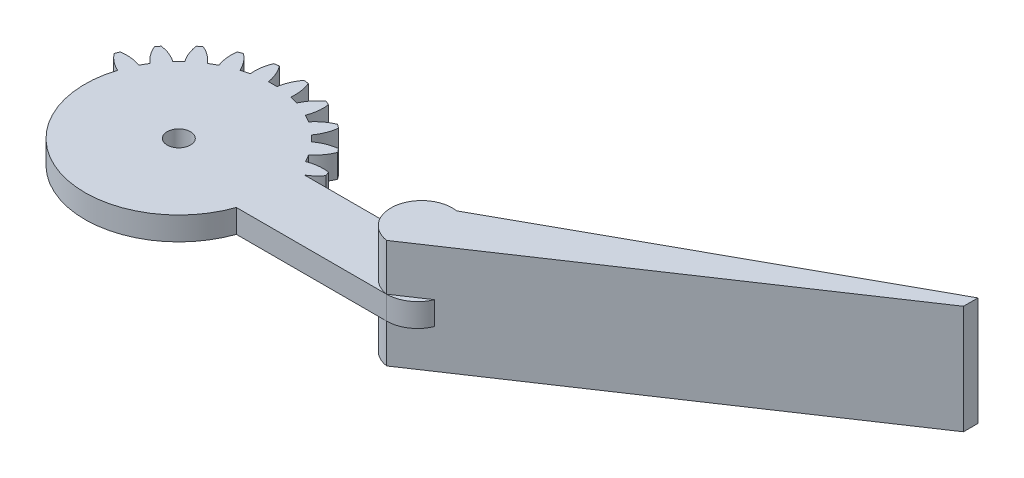
SolidWorks part; units mm, degrees
ref_plane "Front Plane" through (0, 0, 0) normal (0, 0, 1) x (1, 0, 0)
ref_plane "Top Plane" through (0, 0, 0) normal (0, 1, 0) x (1, 0, 0)
ref_plane "Right Plane" through (0, 0, 0) normal (1, 0, 0) x (0, 0, -1)
sketch "Sketch1" plane through (0, 0, 0) normal (0, 1, 0) x (1, 0, 0)
  line L0 (20.6437, 4) -> (2.0816, 4)
  line L1 (2.0816, -4) -> (20.6437, -4)
  arc A0 (2.0816, 4) -> (3.5217, 5.3071) centre (-0.7683, 8.5867) ccw
  arc A1 (3.5217, 5.3071) -> (3.2829, 5.8838) centre (-10.1063, 0) ccw
  arc A2 (3.2829, 5.8838) -> (0.6271, 5.5703) centre (2.5684, 0.5313) ccw
  arc A3 (0.6271, 5.5703) -> (0.0844, 6.5103) centre (-10.1063, 0) ccw
  arc A4 (0.0844, 6.5103) -> (1.6838, 8.6535) centre (-3.3089, 10.711) ccw
  arc A5 (1.6838, 8.6535) -> (1.3038, 9.1487) centre (-10.1063, 0) ccw
  arc A6 (1.3038, 9.1487) -> (-1.1803, 8.1585) centre (1.999, 3.7936) ccw
  arc A7 (-1.1803, 8.1585) -> (-1.9479, 8.926) centre (-10.1063, 0) ccw
  arc A8 (-1.9479, 8.926) -> (-0.9576, 11.4102) centre (-6.3127, 12.1053) ccw
  arc A9 (-0.9576, 11.4102) -> (-1.4528, 11.7901) centre (-10.1063, 0) ccw
  arc A10 (-1.4528, 11.7901) -> (-3.596, 10.1907) centre (0.6046, 6.7975) ccw
  arc A11 (-3.596, 10.1907) -> (-4.5361, 10.7334) centre (-10.1063, 0) ccw
  arc A12 (-4.5361, 10.7334) -> (-4.2225, 13.3892) centre (-9.5751, 12.6747) ccw
  arc A13 (-4.2225, 13.3892) -> (-4.7992, 13.6281) centre (-10.1063, 0) ccw
  arc A14 (-4.7992, 13.6281) -> (-6.4554, 11.5285) centre (-1.5196, 9.3381) ccw
  arc A15 (-6.4554, 11.5285) -> (-7.5039, 11.8094) centre (-10.1063, 0) ccw
  arc A16 (-7.5039, 11.8094) -> (-7.8884, 14.4558) centre (-12.8736, 12.3803) ccw
  arc A17 (-7.8884, 14.4558) -> (-8.5072, 14.5373) centre (-10.1063, 0) ccw
  arc A18 (-8.5072, 14.5373) -> (-9.5636, 12.0806) centre (-4.2291, 11.2423) ccw
  arc A19 (-9.5636, 12.0806) -> (-10.6491, 12.0806) centre (-10.1063, 0) ccw
  arc A20 (-10.6491, 12.0806) -> (-11.7054, 14.5373) centre (-15.9836, 11.2423) ccw
  arc A21 (-11.7054, 14.5373) -> (-12.3243, 14.4558) centre (-10.1063, 0) ccw
  arc A22 (-12.3243, 14.4558) -> (-12.7088, 11.8094) centre (-7.3391, 12.3803) ccw
  arc A23 (-12.7088, 11.8094) -> (-13.7573, 11.5285) centre (-10.1063, 0) ccw
  arc A24 (-13.7573, 11.5285) -> (-15.4135, 13.6281) centre (-18.6931, 9.3381) ccw
  arc A25 (-15.4135, 13.6281) -> (-15.9901, 13.3892) centre (-10.1063, 0) ccw
  arc A26 (-15.9901, 13.3892) -> (-15.6766, 10.7334) centre (-10.6376, 12.6747) ccw
  arc A27 (-15.6766, 10.7334) -> (-16.6166, 10.1907) centre (-10.1063, 0) ccw
  arc A28 (-16.6166, 10.1907) -> (-18.7599, 11.7901) centre (-20.8173, 6.7975) ccw
  arc A29 (-18.7599, 11.7901) -> (-19.255, 11.4102) centre (-10.1063, 0) ccw
  arc A30 (-19.255, 11.4102) -> (-18.2648, 8.926) centre (-13.9, 12.1053) ccw
  arc A31 (-18.2648, 8.926) -> (-19.0324, 8.1585) centre (-10.1063, 0) ccw
  arc A32 (-19.0324, 8.1585) -> (-21.5165, 9.1487) centre (-22.2117, 3.7936) ccw
  arc A33 (-21.5165, 9.1487) -> (-21.8965, 8.6535) centre (-10.1063, 0) ccw
  arc A34 (-21.8965, 8.6535) -> (-20.2971, 6.5103) centre (-16.9038, 10.711) ccw
  arc A35 (-20.2971, 6.5103) -> (-20.8398, 5.5703) centre (-10.1063, 0) ccw
  arc A36 (-20.8398, 5.5703) -> (-23.4956, 5.8838) centre (-22.7811, 0.5313) ccw
  arc A37 (-23.4956, 5.8838) -> (-23.7344, 5.3071) centre (-10.1063, 0) ccw
  arc A38 (-23.7344, 5.3071) -> (-21.6348, 3.6509) centre (-19.4444, 8.5867) ccw
  arc A39 (-21.6348, 3.6509) -> (-21.9157, 2.6025) centre (-10.1063, 0) ccw
  arc A40 (-21.9157, 2.6025) -> (-24.5622, 2.2179) centre (-22.4867, -2.7673) ccw
  arc A41 (-24.5622, 2.2179) -> (-24.6437, 1.5991) centre (-10.1063, 0) ccw
  arc A42 (-24.6437, 1.5991) -> (-22.1869, 0.5427) centre (-21.3486, 5.8773) ccw
  arc A43 (-22.1869, 0.5427) -> (-22.1869, -0.5427) centre (-10.1063, 0) ccw
  arc A44 (-22.1869, -0.5427) -> (-24.6437, -1.5991) centre (-21.3486, -5.8773) ccw
  arc A45 (-24.6437, -1.5991) -> (-24.5622, -2.2179) centre (-10.1063, 0) ccw
  arc A46 (-24.5622, -2.2179) -> (-21.9157, -2.6025) centre (-22.4867, 2.7673) ccw
  arc A47 (-21.9157, -2.6025) -> (-21.6348, -3.6509) centre (-10.1063, 0) ccw
  arc A48 (-21.6348, -3.6509) -> (-23.7344, -5.3071) centre (-19.4444, -8.5867) ccw
  arc A49 (-23.7344, -5.3071) -> (-23.4956, -5.8838) centre (-10.1063, 0) ccw
  arc A50 (-23.4956, -5.8838) -> (-20.8398, -5.5703) centre (-22.7811, -0.5313) ccw
  arc A51 (-20.8398, -5.5703) -> (-20.2971, -6.5103) centre (-10.1063, 0) ccw
  arc A52 (-20.2971, -6.5103) -> (-21.8965, -8.6535) centre (-16.9038, -10.711) ccw
  arc A53 (-21.8965, -8.6535) -> (-21.5165, -9.1487) centre (-10.1063, 0) ccw
  arc A54 (-21.5165, -9.1487) -> (-19.0324, -8.1585) centre (-22.2117, -3.7936) ccw
  arc A55 (-19.0324, -8.1585) -> (-18.2648, -8.926) centre (-10.1063, 0) ccw
  arc A56 (-18.2648, -8.926) -> (-19.255, -11.4102) centre (-13.9, -12.1053) ccw
  arc A57 (-19.255, -11.4102) -> (-18.7599, -11.7901) centre (-10.1063, 0) ccw
  arc A58 (-18.7599, -11.7901) -> (-16.6166, -10.1907) centre (-20.8173, -6.7975) ccw
  arc A59 (-16.6166, -10.1907) -> (-15.6766, -10.7334) centre (-10.1063, 0) ccw
  arc A60 (-15.6766, -10.7334) -> (-15.9901, -13.3892) centre (-10.6376, -12.6747) ccw
  arc A61 (-15.9901, -13.3892) -> (-15.4135, -13.6281) centre (-10.1063, 0) ccw
  arc A62 (-15.4135, -13.6281) -> (-13.7573, -11.5285) centre (-18.6931, -9.3381) ccw
  arc A63 (-13.7573, -11.5285) -> (-12.7088, -11.8094) centre (-10.1063, 0) ccw
  arc A64 (-12.7088, -11.8094) -> (-12.3243, -14.4558) centre (-7.3391, -12.3803) ccw
  arc A65 (-12.3243, -14.4558) -> (-11.7054, -14.5373) centre (-10.1063, 0) ccw
  arc A66 (-11.7054, -14.5373) -> (-10.6491, -12.0806) centre (-15.9836, -11.2423) ccw
  arc A67 (-10.6491, -12.0806) -> (-9.5636, -12.0806) centre (-10.1063, 0) ccw
  arc A68 (-9.5636, -12.0806) -> (-8.5072, -14.5373) centre (-4.2291, -11.2423) ccw
  arc A69 (-8.5072, -14.5373) -> (-7.8884, -14.4558) centre (-10.1063, 0) ccw
  arc A70 (-7.8884, -14.4558) -> (-7.5039, -11.8094) centre (-12.8736, -12.3803) ccw
  arc A71 (-7.5039, -11.8094) -> (-6.4554, -11.5285) centre (-10.1063, 0) ccw
  arc A72 (-6.4554, -11.5285) -> (-4.7992, -13.6281) centre (-1.5196, -9.3381) ccw
  arc A73 (-4.7992, -13.6281) -> (-4.2225, -13.3892) centre (-10.1063, 0) ccw
  arc A74 (-4.2225, -13.3892) -> (-4.5361, -10.7334) centre (-9.5751, -12.6747) ccw
  arc A75 (-4.5361, -10.7334) -> (-3.596, -10.1907) centre (-10.1063, 0) ccw
  arc A76 (-3.596, -10.1907) -> (-1.4528, -11.7901) centre (0.6046, -6.7975) ccw
  arc A77 (-1.4528, -11.7901) -> (-0.9576, -11.4102) centre (-10.1063, 0) ccw
  arc A78 (-0.9576, -11.4102) -> (-1.9479, -8.926) centre (-6.3127, -12.1053) ccw
  arc A79 (-1.9479, -8.926) -> (-1.1803, -8.1585) centre (-10.1063, 0) ccw
  arc A80 (-1.1803, -8.1585) -> (1.3038, -9.1487) centre (1.999, -3.7936) ccw
  arc A81 (1.3038, -9.1487) -> (1.6838, -8.6535) centre (-10.1063, 0) ccw
  arc A82 (1.6838, -8.6535) -> (0.0844, -6.5103) centre (-3.3089, -10.711) ccw
  arc A83 (0.0844, -6.5103) -> (0.6271, -5.5703) centre (-10.1063, 0) ccw
  arc A84 (0.6271, -5.5703) -> (3.2829, -5.8838) centre (2.5684, -0.5313) ccw
  arc A85 (3.2829, -5.8838) -> (3.5217, -5.3071) centre (-10.1063, 0) ccw
  arc A86 (3.5217, -5.3071) -> (2.0816, -4) centre (-0.7683, -8.5867) ccw
  arc A87 (20.6437, -4) -> (20.6437, 4) centre (20.6437, 0) ccw
  circle A88 centre (-10.1063, 0) radius 1.5
  circle A89 centre (20.6437, 0) radius 1.5
  dimension "D1" = 3
  dimension "D2" = 3
extrude "Boss-Extrude1" add sketch "Sketch1" along normal blind 3
sketch "Sketch2" plane through (0, 3, 0) normal (0, 1, 0) x (1, 0, 0)
  line L0 (2.0816, -4) -> (1.3057, -4)
  line L2 (20.6437, 4) -> (2.0816, 4)
  line L3 (2.0816, -4) -> (20.6437, -4)
  line L4 (20.6437, 4) -> (2.0816, 4)
  line L5 (2.0816, -4) -> (20.6437, -4)
  circle A0 centre (-10.1063, 0) radius 12.0927
  arc A88 (20.6437, -4) -> (20.6437, 4) centre (20.6437, 0) ccw
  arc A89 (2.0816, 4) -> (3.5217, 5.3071) centre (-0.7683, 8.5867) ccw
  arc A90 (3.5217, 5.3071) -> (3.2829, 5.8838) centre (-10.1063, 0) ccw
  arc A91 (3.2829, 5.8838) -> (0.6271, 5.5703) centre (2.5684, 0.5313) ccw
  arc A92 (0.6271, 5.5703) -> (0.0844, 6.5103) centre (-10.1063, 0) ccw
  arc A93 (0.0844, 6.5103) -> (1.6838, 8.6535) centre (-3.3089, 10.711) ccw
  arc A94 (1.6838, 8.6535) -> (1.3038, 9.1487) centre (-10.1063, 0) ccw
  arc A95 (1.3038, 9.1487) -> (-1.1803, 8.1585) centre (1.999, 3.7936) ccw
  arc A96 (-1.1803, 8.1585) -> (-1.9479, 8.926) centre (-10.1063, 0) ccw
  arc A97 (-1.9479, 8.926) -> (-0.9576, 11.4102) centre (-6.3127, 12.1053) ccw
  arc A98 (-0.9576, 11.4102) -> (-1.4528, 11.7901) centre (-10.1063, 0) ccw
  arc A99 (-1.4528, 11.7901) -> (-3.596, 10.1907) centre (0.6046, 6.7975) ccw
  arc A100 (-3.596, 10.1907) -> (-4.5361, 10.7334) centre (-10.1063, 0) ccw
  arc A101 (-4.5361, 10.7334) -> (-4.2225, 13.3892) centre (-9.5751, 12.6747) ccw
  arc A102 (-4.2225, 13.3892) -> (-4.7992, 13.6281) centre (-10.1063, 0) ccw
  arc A103 (-4.7992, 13.6281) -> (-6.4554, 11.5285) centre (-1.5196, 9.3381) ccw
  arc A104 (-6.4554, 11.5285) -> (-7.5039, 11.8094) centre (-10.1063, 0) ccw
  arc A105 (-7.5039, 11.8094) -> (-7.8884, 14.4558) centre (-12.8736, 12.3803) ccw
  arc A106 (-7.8884, 14.4558) -> (-8.5072, 14.5373) centre (-10.1063, 0) ccw
  arc A107 (-8.5072, 14.5373) -> (-9.5636, 12.0806) centre (-4.2291, 11.2423) ccw
  arc A108 (-9.5636, 12.0806) -> (-10.6491, 12.0806) centre (-10.1063, 0) ccw
  arc A109 (-10.6491, 12.0806) -> (-11.7054, 14.5373) centre (-15.9836, 11.2423) ccw
  arc A110 (-11.7054, 14.5373) -> (-12.3243, 14.4558) centre (-10.1063, 0) ccw
  arc A111 (-12.3243, 14.4558) -> (-12.7088, 11.8094) centre (-7.3391, 12.3803) ccw
  arc A112 (-12.7088, 11.8094) -> (-13.7573, 11.5285) centre (-10.1063, 0) ccw
  arc A113 (-13.7573, 11.5285) -> (-15.4135, 13.6281) centre (-18.6931, 9.3381) ccw
  arc A114 (-15.4135, 13.6281) -> (-15.9901, 13.3892) centre (-10.1063, 0) ccw
  arc A115 (-15.9901, 13.3892) -> (-15.6766, 10.7334) centre (-10.6376, 12.6747) ccw
  arc A116 (-15.6766, 10.7334) -> (-16.6166, 10.1907) centre (-10.1063, 0) ccw
  arc A117 (-16.6166, 10.1907) -> (-18.7599, 11.7901) centre (-20.8173, 6.7975) ccw
  arc A118 (-18.7599, 11.7901) -> (-19.255, 11.4102) centre (-10.1063, 0) ccw
  arc A119 (-19.255, 11.4102) -> (-18.2648, 8.926) centre (-13.9, 12.1053) ccw
  arc A120 (-18.2648, 8.926) -> (-19.0324, 8.1585) centre (-10.1063, 0) ccw
  arc A121 (-19.0324, 8.1585) -> (-21.5165, 9.1487) centre (-22.2117, 3.7936) ccw
  arc A122 (-21.5165, 9.1487) -> (-21.8965, 8.6535) centre (-10.1063, 0) ccw
  arc A123 (-21.8965, 8.6535) -> (-20.2971, 6.5103) centre (-16.9038, 10.711) ccw
  arc A124 (-20.2971, 6.5103) -> (-20.8398, 5.5703) centre (-10.1063, 0) ccw
  arc A125 (-20.8398, 5.5703) -> (-23.4956, 5.8838) centre (-22.7811, 0.5313) ccw
  arc A126 (-23.4956, 5.8838) -> (-23.7344, 5.3071) centre (-10.1063, 0) ccw
  arc A127 (-23.7344, 5.3071) -> (-21.6348, 3.6509) centre (-19.4444, 8.5867) ccw
  arc A128 (-21.6348, 3.6509) -> (-21.9157, 2.6025) centre (-10.1063, 0) ccw
  arc A129 (-21.9157, 2.6025) -> (-24.5622, 2.2179) centre (-22.4867, -2.7673) ccw
  arc A130 (-24.5622, 2.2179) -> (-24.6437, 1.5991) centre (-10.1063, 0) ccw
  arc A131 (-24.6437, 1.5991) -> (-22.1869, 0.5427) centre (-21.3486, 5.8773) ccw
  arc A132 (-22.1869, 0.5427) -> (-22.1869, -0.5427) centre (-10.1063, 0) ccw
  arc A133 (-22.1869, -0.5427) -> (-24.6437, -1.5991) centre (-21.3486, -5.8773) ccw
  arc A134 (-24.6437, -1.5991) -> (-24.5622, -2.2179) centre (-10.1063, 0) ccw
  arc A135 (-24.5622, -2.2179) -> (-21.9157, -2.6025) centre (-22.4867, 2.7673) ccw
  arc A136 (-21.9157, -2.6025) -> (-21.6348, -3.6509) centre (-10.1063, 0) ccw
  arc A137 (-21.6348, -3.6509) -> (-23.7344, -5.3071) centre (-19.4444, -8.5867) ccw
  arc A138 (-23.7344, -5.3071) -> (-23.4956, -5.8838) centre (-10.1063, 0) ccw
  arc A139 (-23.4956, -5.8838) -> (-20.8398, -5.5703) centre (-22.7811, -0.5313) ccw
  arc A140 (-20.8398, -5.5703) -> (-20.2971, -6.5103) centre (-10.1063, 0) ccw
  arc A141 (-20.2971, -6.5103) -> (-21.8965, -8.6535) centre (-16.9038, -10.711) ccw
  arc A142 (-21.8965, -8.6535) -> (-21.5165, -9.1487) centre (-10.1063, 0) ccw
  arc A143 (-21.5165, -9.1487) -> (-19.0324, -8.1585) centre (-22.2117, -3.7936) ccw
  arc A144 (-19.0324, -8.1585) -> (-18.2648, -8.926) centre (-10.1063, 0) ccw
  arc A145 (-18.2648, -8.926) -> (-19.255, -11.4102) centre (-13.9, -12.1053) ccw
  arc A146 (-19.255, -11.4102) -> (-18.7599, -11.7901) centre (-10.1063, 0) ccw
  arc A147 (-18.7599, -11.7901) -> (-16.6166, -10.1907) centre (-20.8173, -6.7975) ccw
  arc A148 (-16.6166, -10.1907) -> (-15.6766, -10.7334) centre (-10.1063, 0) ccw
  arc A149 (-15.6766, -10.7334) -> (-15.9901, -13.3892) centre (-10.6376, -12.6747) ccw
  arc A150 (-15.9901, -13.3892) -> (-15.4135, -13.6281) centre (-10.1063, 0) ccw
  arc A151 (-15.4135, -13.6281) -> (-13.7573, -11.5285) centre (-18.6931, -9.3381) ccw
  arc A152 (-13.7573, -11.5285) -> (-12.7088, -11.8094) centre (-10.1063, 0) ccw
  arc A153 (-12.7088, -11.8094) -> (-12.3243, -14.4558) centre (-7.3391, -12.3803) ccw
  arc A154 (-12.3243, -14.4558) -> (-11.7054, -14.5373) centre (-10.1063, 0) ccw
  arc A155 (-11.7054, -14.5373) -> (-10.6491, -12.0806) centre (-15.9836, -11.2423) ccw
  arc A156 (-10.6491, -12.0806) -> (-9.5636, -12.0806) centre (-10.1063, 0) ccw
  arc A157 (-9.5636, -12.0806) -> (-8.5072, -14.5373) centre (-4.2291, -11.2423) ccw
  arc A158 (-8.5072, -14.5373) -> (-7.8884, -14.4558) centre (-10.1063, 0) ccw
  arc A159 (-7.8884, -14.4558) -> (-7.5039, -11.8094) centre (-12.8736, -12.3803) ccw
  arc A160 (-7.5039, -11.8094) -> (-6.4554, -11.5285) centre (-10.1063, 0) ccw
  arc A161 (-6.4554, -11.5285) -> (-4.7992, -13.6281) centre (-1.5196, -9.3381) ccw
  arc A162 (-4.7992, -13.6281) -> (-4.2225, -13.3892) centre (-10.1063, 0) ccw
  arc A163 (-4.2225, -13.3892) -> (-4.5361, -10.7334) centre (-9.5751, -12.6747) ccw
  arc A164 (-4.5361, -10.7334) -> (-3.596, -10.1907) centre (-10.1063, 0) ccw
  arc A165 (-3.596, -10.1907) -> (-1.4528, -11.7901) centre (0.6046, -6.7975) ccw
  arc A166 (-1.4528, -11.7901) -> (-0.9576, -11.4102) centre (-10.1063, 0) ccw
  arc A167 (-0.9576, -11.4102) -> (-1.9479, -8.926) centre (-6.3127, -12.1053) ccw
  arc A168 (-1.9479, -8.926) -> (-1.1803, -8.1585) centre (-10.1063, 0) ccw
  arc A169 (-1.1803, -8.1585) -> (1.3038, -9.1487) centre (1.999, -3.7936) ccw
  arc A170 (1.3038, -9.1487) -> (1.6838, -8.6535) centre (-10.1063, 0) ccw
  arc A171 (1.6838, -8.6535) -> (0.0844, -6.5103) centre (-3.3089, -10.711) ccw
  arc A172 (0.0844, -6.5103) -> (0.6271, -5.5703) centre (-10.1063, 0) ccw
  arc A173 (0.6271, -5.5703) -> (3.2829, -5.8838) centre (2.5684, -0.5313) ccw
  arc A174 (3.2829, -5.8838) -> (3.5217, -5.3071) centre (-10.1063, 0) ccw
  arc A175 (3.5217, -5.3071) -> (2.0816, -4) centre (-0.7683, -8.5867) ccw
  arc A176 (20.6437, -4) -> (20.6437, 4) centre (20.6437, 0) ccw
  arc A177 (2.0816, 4) -> (3.5217, 5.3071) centre (-0.7683, 8.5867) ccw
  arc A178 (3.5217, 5.3071) -> (3.2829, 5.8838) centre (-10.1063, 0) ccw
  arc A179 (3.2829, 5.8838) -> (0.6271, 5.5703) centre (2.5684, 0.5313) ccw
  arc A180 (0.6271, 5.5703) -> (0.0844, 6.5103) centre (-10.1063, 0) ccw
  arc A181 (0.0844, 6.5103) -> (1.6838, 8.6535) centre (-3.3089, 10.711) ccw
  arc A182 (1.6838, 8.6535) -> (1.3038, 9.1487) centre (-10.1063, 0) ccw
  arc A183 (1.3038, 9.1487) -> (-1.1803, 8.1585) centre (1.999, 3.7936) ccw
  arc A184 (-1.1803, 8.1585) -> (-1.9479, 8.926) centre (-10.1063, 0) ccw
  arc A185 (-1.9479, 8.926) -> (-0.9576, 11.4102) centre (-6.3127, 12.1053) ccw
  arc A186 (-0.9576, 11.4102) -> (-1.4528, 11.7901) centre (-10.1063, 0) ccw
  arc A187 (-1.4528, 11.7901) -> (-3.596, 10.1907) centre (0.6046, 6.7975) ccw
  arc A188 (-3.596, 10.1907) -> (-4.5361, 10.7334) centre (-10.1063, 0) ccw
  arc A189 (-4.5361, 10.7334) -> (-4.2225, 13.3892) centre (-9.5751, 12.6747) ccw
  arc A190 (-4.2225, 13.3892) -> (-4.7992, 13.6281) centre (-10.1063, 0) ccw
  arc A191 (-4.7992, 13.6281) -> (-6.4554, 11.5285) centre (-1.5196, 9.3381) ccw
  arc A192 (-6.4554, 11.5285) -> (-7.5039, 11.8094) centre (-10.1063, 0) ccw
  arc A193 (-7.5039, 11.8094) -> (-7.8884, 14.4558) centre (-12.8736, 12.3803) ccw
  arc A194 (-7.8884, 14.4558) -> (-8.5072, 14.5373) centre (-10.1063, 0) ccw
  arc A195 (-8.5072, 14.5373) -> (-9.5636, 12.0806) centre (-4.2291, 11.2423) ccw
  arc A196 (-9.5636, 12.0806) -> (-10.6491, 12.0806) centre (-10.1063, 0) ccw
  arc A197 (-10.6491, 12.0806) -> (-11.7054, 14.5373) centre (-15.9836, 11.2423) ccw
  arc A198 (-11.7054, 14.5373) -> (-12.3243, 14.4558) centre (-10.1063, 0) ccw
  arc A199 (-12.3243, 14.4558) -> (-12.7088, 11.8094) centre (-7.3391, 12.3803) ccw
  arc A200 (-12.7088, 11.8094) -> (-13.7573, 11.5285) centre (-10.1063, 0) ccw
  arc A201 (-13.7573, 11.5285) -> (-15.4135, 13.6281) centre (-18.6931, 9.3381) ccw
  arc A202 (-15.4135, 13.6281) -> (-15.9901, 13.3892) centre (-10.1063, 0) ccw
  arc A203 (-15.9901, 13.3892) -> (-15.6766, 10.7334) centre (-10.6376, 12.6747) ccw
  arc A204 (-15.6766, 10.7334) -> (-16.6166, 10.1907) centre (-10.1063, 0) ccw
  arc A205 (-16.6166, 10.1907) -> (-18.7599, 11.7901) centre (-20.8173, 6.7975) ccw
  arc A206 (-18.7599, 11.7901) -> (-19.255, 11.4102) centre (-10.1063, 0) ccw
  arc A207 (-19.255, 11.4102) -> (-18.2648, 8.926) centre (-13.9, 12.1053) ccw
  arc A208 (-18.2648, 8.926) -> (-19.0324, 8.1585) centre (-10.1063, 0) ccw
  arc A209 (-19.0324, 8.1585) -> (-21.5165, 9.1487) centre (-22.2117, 3.7936) ccw
  arc A210 (-21.5165, 9.1487) -> (-21.8965, 8.6535) centre (-10.1063, 0) ccw
  arc A211 (-21.8965, 8.6535) -> (-20.2971, 6.5103) centre (-16.9038, 10.711) ccw
  arc A212 (-20.2971, 6.5103) -> (-20.8398, 5.5703) centre (-10.1063, 0) ccw
  arc A213 (-20.8398, 5.5703) -> (-23.4956, 5.8838) centre (-22.7811, 0.5313) ccw
  arc A214 (-23.4956, 5.8838) -> (-23.7344, 5.3071) centre (-10.1063, 0) ccw
  arc A215 (-23.7344, 5.3071) -> (-21.6348, 3.6509) centre (-19.4444, 8.5867) ccw
  arc A216 (-21.6348, 3.6509) -> (-21.9157, 2.6025) centre (-10.1063, 0) ccw
  arc A217 (-21.9157, 2.6025) -> (-24.5622, 2.2179) centre (-22.4867, -2.7673) ccw
  arc A218 (-24.5622, 2.2179) -> (-24.6437, 1.5991) centre (-10.1063, 0) ccw
  arc A219 (-24.6437, 1.5991) -> (-22.1869, 0.5427) centre (-21.3486, 5.8773) ccw
  arc A220 (-22.1869, 0.5427) -> (-22.1869, -0.5427) centre (-10.1063, 0) ccw
  arc A221 (-22.1869, -0.5427) -> (-24.6437, -1.5991) centre (-21.3486, -5.8773) ccw
  arc A222 (-24.6437, -1.5991) -> (-24.5622, -2.2179) centre (-10.1063, 0) ccw
  arc A223 (-24.5622, -2.2179) -> (-21.9157, -2.6025) centre (-22.4867, 2.7673) ccw
  arc A224 (-21.9157, -2.6025) -> (-21.6348, -3.6509) centre (-10.1063, 0) ccw
  arc A225 (-21.6348, -3.6509) -> (-23.7344, -5.3071) centre (-19.4444, -8.5867) ccw
  arc A226 (-23.7344, -5.3071) -> (-23.4956, -5.8838) centre (-10.1063, 0) ccw
  arc A227 (-23.4956, -5.8838) -> (-20.8398, -5.5703) centre (-22.7811, -0.5313) ccw
  arc A228 (-20.8398, -5.5703) -> (-20.2971, -6.5103) centre (-10.1063, 0) ccw
  arc A229 (-20.2971, -6.5103) -> (-21.8965, -8.6535) centre (-16.9038, -10.711) ccw
  arc A230 (-21.8965, -8.6535) -> (-21.5165, -9.1487) centre (-10.1063, 0) ccw
  arc A231 (-21.5165, -9.1487) -> (-19.0324, -8.1585) centre (-22.2117, -3.7936) ccw
  arc A232 (-19.0324, -8.1585) -> (-18.2648, -8.926) centre (-10.1063, 0) ccw
  arc A233 (-18.2648, -8.926) -> (-19.255, -11.4102) centre (-13.9, -12.1053) ccw
  arc A234 (-19.255, -11.4102) -> (-18.7599, -11.7901) centre (-10.1063, 0) ccw
  arc A235 (-18.7599, -11.7901) -> (-16.6166, -10.1907) centre (-20.8173, -6.7975) ccw
  arc A236 (-16.6166, -10.1907) -> (-15.6766, -10.7334) centre (-10.1063, 0) ccw
  arc A237 (-15.6766, -10.7334) -> (-15.9901, -13.3892) centre (-10.6376, -12.6747) ccw
  arc A238 (-15.9901, -13.3892) -> (-15.4135, -13.6281) centre (-10.1063, 0) ccw
  arc A239 (-15.4135, -13.6281) -> (-13.7573, -11.5285) centre (-18.6931, -9.3381) ccw
  arc A240 (-13.7573, -11.5285) -> (-12.7088, -11.8094) centre (-10.1063, 0) ccw
  arc A241 (-12.7088, -11.8094) -> (-12.3243, -14.4558) centre (-7.3391, -12.3803) ccw
  arc A242 (-12.3243, -14.4558) -> (-11.7054, -14.5373) centre (-10.1063, 0) ccw
  arc A243 (-11.7054, -14.5373) -> (-10.6491, -12.0806) centre (-15.9836, -11.2423) ccw
  arc A244 (-10.6491, -12.0806) -> (-9.5636, -12.0806) centre (-10.1063, 0) ccw
  arc A245 (-9.5636, -12.0806) -> (-8.5072, -14.5373) centre (-4.2291, -11.2423) ccw
  arc A246 (-8.5072, -14.5373) -> (-7.8884, -14.4558) centre (-10.1063, 0) ccw
  arc A247 (-7.8884, -14.4558) -> (-7.5039, -11.8094) centre (-12.8736, -12.3803) ccw
  arc A248 (-7.5039, -11.8094) -> (-6.4554, -11.5285) centre (-10.1063, 0) ccw
  arc A249 (-6.4554, -11.5285) -> (-4.7992, -13.6281) centre (-1.5196, -9.3381) ccw
  arc A250 (-4.7992, -13.6281) -> (-4.2225, -13.3892) centre (-10.1063, 0) ccw
  arc A251 (-4.2225, -13.3892) -> (-4.5361, -10.7334) centre (-9.5751, -12.6747) ccw
  arc A252 (-4.5361, -10.7334) -> (-3.596, -10.1907) centre (-10.1063, 0) ccw
  arc A253 (-3.596, -10.1907) -> (-1.4528, -11.7901) centre (0.6046, -6.7975) ccw
  arc A254 (-1.4528, -11.7901) -> (-0.9576, -11.4102) centre (-10.1063, 0) ccw
  arc A255 (-0.9576, -11.4102) -> (-1.9479, -8.926) centre (-6.3127, -12.1053) ccw
  arc A256 (-1.9479, -8.926) -> (-1.1803, -8.1585) centre (-10.1063, 0) ccw
  arc A257 (-1.1803, -8.1585) -> (1.3038, -9.1487) centre (1.999, -3.7936) ccw
  arc A258 (1.3038, -9.1487) -> (1.6838, -8.6535) centre (-10.1063, 0) ccw
  arc A259 (1.6838, -8.6535) -> (0.0844, -6.5103) centre (-3.3089, -10.711) ccw
  arc A260 (0.0844, -6.5103) -> (0.6271, -5.5703) centre (-10.1063, 0) ccw
  arc A261 (0.6271, -5.5703) -> (3.2829, -5.8838) centre (2.5684, -0.5313) ccw
  arc A262 (3.2829, -5.8838) -> (3.5217, -5.3071) centre (-10.1063, 0) ccw
  arc A263 (3.5217, -5.3071) -> (2.0816, -4) centre (-0.7683, -8.5867) ccw
  dimension "D1" = 0
extrude "Cut-Extrude1" cut sketch "Sketch2" against normal blind 10 contours A222 A223 A0 A221 | A226 A227 A0 A225 | A230 A231 A0 A229 | A234 A235 A0 A233 | A238 A239 A0 A237 | A242 A243 A0 A241 | A246 A247 A0 A245 | A250 A251 A0 A249 | A254 A255 A0 A253 | A258 A259 A0 A257 | A262 A263 L0 A0 A261 | A218 A219 A0 A217 region at (2.066, 3, 5.0775) region at (0.3325, 3, 8.01) region at (-2.0963, 3, 10.4389) region at (-5.071, 3, 12.1563) region at (-8.3889, 3, 13.0454) region at (-11.8238, 3, 13.0454) region at (-15.1417, 3, 12.1563) region at (-18.1164, 3, 10.4389) region at (-20.5452, 3, 8.01) region at (-22.2627, 3, 5.0353) region at (-23.1517, 3, 1.7175) region at (-23.1517, 3, -1.7175)
sketch "Sketch3" plane through (0, 3, 0) normal (0, 1, 0) x (1, 0, 0)
  line L0 (21.8635, 3.8095) -> (65.1258, 27.6605)
  line L1 (20.6437, -4) -> (65.1258, 25.79)
  line L2 (65.1258, 25.79) -> (65.1258, 27.6605)
  arc A0 (20.6437, -4) -> (20.6437, 4) centre (20.6437, 0) ccw construction
  arc A1 (20.6437, -4) -> (21.8635, 3.8095) centre (21.2536, -0.0953) cw
extrude "Boss-Extrude2" add sketch "Sketch3" against normal blind 8 and the other way blind 6
